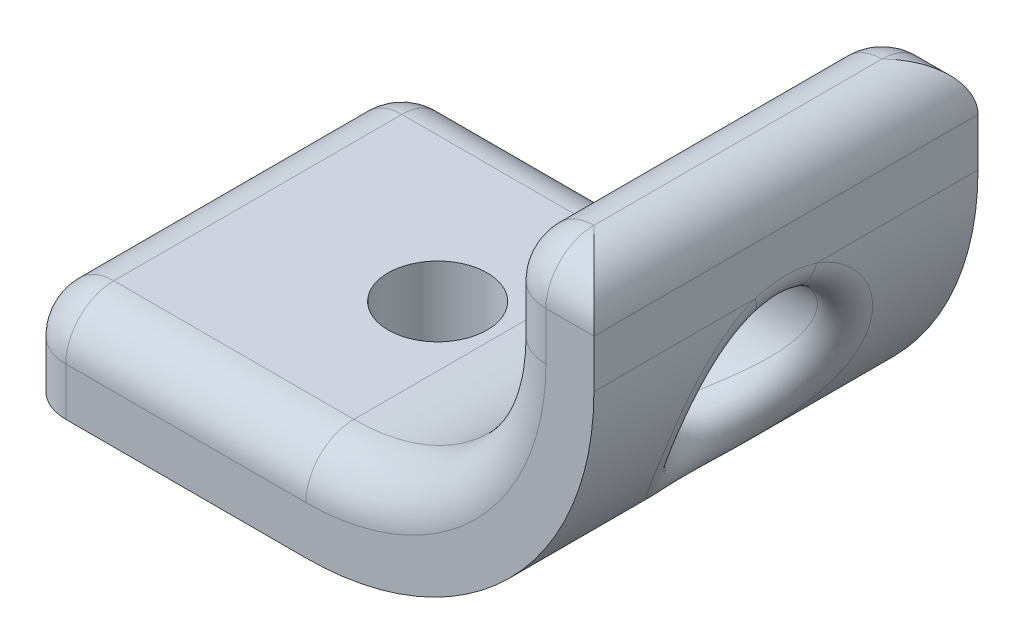
SolidWorks part; units mm, degrees
ref_plane "Front Plane" through (0, 0, 0) normal (0, 0, 1) x (1, 0, 0)
ref_plane "Top Plane" through (0, 0, 0) normal (0, 1, 0) x (1, 0, 0)
ref_plane "Right Plane" through (0, 0, 0) normal (1, 0, 0) x (0, 0, -1)
sketch "Sketch2" plane through (0, 0, 0) normal (0, 0, 1) x (1, 0, 0)
  line L0 (0, 0) -> (-23.7258, 0)
  line L1 (-23.7258, 0) -> (-23.7258, 10)
  line L2 (-23.7258, 10) -> (6.2742, 10)
  line L3 (26.2742, 30) -> (26.2742, 40)
  line L4 (26.2742, 40) -> (36.2742, 40)
  line L5 (36.2742, 40) -> (36.2742, 30)
  line L6 (6.2742, 0) -> (0, 0)
  arc A0 (6.2742, 10) -> (26.2742, 30) centre (6.2742, 30) ccw
  arc A1 (36.2742, 30) -> (6.2742, 0) centre (6.2742, 30) cw
  point P2 (16.2742, 31.1243)
  point P10 (0, 0)
  point P12 (0, 0)
  point P13 (0, 0)
  point P14 (50.8567, 87.2701)
  point P15 (0, 0)
  point P16 (0, 0)
  point P17 (0, 0)
  point P18 (0, 0)
  dimension "D5" = 20
  dimension "D1" = 10
  dimension "D2" = 10
  dimension "D3" = 30
  dimension "D4" = 40
extrude "Boss-Extrude1" add sketch "Sketch2" along normal blind 40
sketch "Sketch3" plane through (0, 10, 0) normal (0, 1, 0) x (1, 0, 0)
  circle A0 centre (0, -20) radius 5.1594
  dimension "D1" = 10.3187
extrude "Cut-Extrude1" cut sketch "Sketch3" against normal through all contours A0
sketch "Sketch4" plane through (36.2742, 0, 0) normal (1, 0, 0) x (0, 0, -1)
  line L1 (-40, 0) -> (0, 0) construction
  line L2 (-40, 40) -> (0, 40) construction
  line L3 (-40, 0) -> (0, 0)
  line L4 (-40, 40) -> (0, 40)
  line L5 (-20, 40) -> (-20, 0)
  circle A0 centre (-20, 20) radius 7.5
  point P8 (-20, 20)
  dimension "D1" = 15
extrude "Cut-Extrude3" cut sketch "Sketch4" against normal through all contours A0
fillet "Fillet1" radius 5 13 edges at (26.2742, 35, 40) (20.4163, 15.8579, 40) (26.2742, 35, 0) (20.4163, 15.8579, 0) (-8.7258, 10, 40) (-23.7258, 10, 20) (-8.7258, 10, 0) (36.2742, 40, 20) (26.2742, 40, 20) (-23.7258, 5, 40) (-23.7258, 5, 0) (31.2742, 40, 40) (31.2742, 40, 0)
fillet "Fillet2" radius 3 2 edges at (34.9063, 21.0447, 27.4269) (21.4026, 16.9183, 26.8376)
